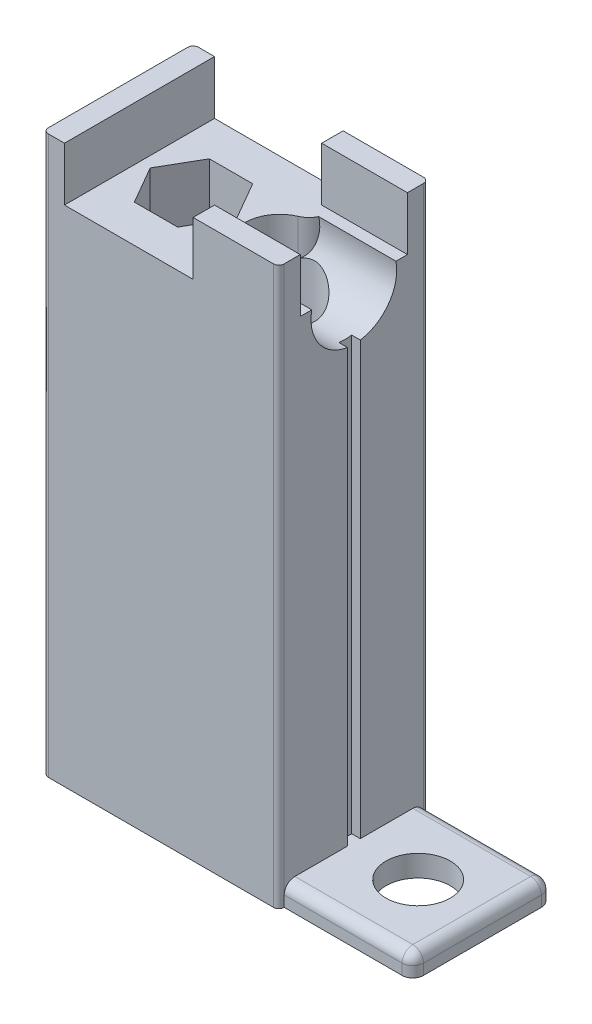
SolidWorks part; units mm, degrees
ref_plane "Front Plane" through (0, 0, 0) normal (0, 0, 1) x (1, 0, 0)
ref_plane "Top Plane" through (0, 0, 0) normal (0, 1, 0) x (1, 0, 0)
ref_plane "Right Plane" through (0, 0, 0) normal (1, 0, 0) x (0, 0, -1)
sketch "Sketch1" plane through (0, 0, 0) normal (0, 1, 0) x (1, 0, 0)
  line L1 (0, 0) -> (22, 0)
  line L2 (0, 0) -> (0, 14)
  line L3 (0, 14) -> (22, 14)
  line L4 (22, 0) -> (22, 14)
  dimension "D1" = 22
  dimension "D2" = 14
extrude "Boss-Extrude1" add sketch "Sketch1" along normal blind 47
sketch "Sketch2" plane through (0, 47, 0) normal (0, 1, 0) x (1, 0, 0)
  line L0 (22, 0) -> (22, 2)
  line L1 (22, 0) -> (22, 14) construction
  line L2 (0, 14) -> (2, 14)
  line L3 (22, 14) -> (0, 14) construction
  line L4 (2, 14) -> (2, 0)
  line L5 (22, 12) -> (22, 14)
  line L6 (0, 0) -> (22, 0) construction
  line L7 (0, 14) -> (0, 0)
  line L8 (2, 0) -> (0, 0)
  line L9 (22, 14) -> (14, 14)
  line L10 (14, 14) -> (14, 12)
  line L11 (14, 12) -> (22, 12)
  line L12 (22, 2) -> (14, 2)
  line L13 (14, 2) -> (14, 0)
  line L14 (14, 0) -> (22, 0)
  dimension "D1" = 2
  dimension "D2" = 2
  dimension "D3" = 8
  dimension "D4" = 8
  dimension "D5" = 2
extrude "Boss-Extrude2" add sketch "Sketch2" along normal blind 5
sketch "Sketch3" plane through (0, 47, 0) normal (0, 1, 0) x (1, 0, 0)
  line L0 (2, 0) -> (2, 14) construction
  line L2 (0, 7) -> (22, 7) construction
  line L4 (0, 14) -> (0, 0) construction
  line L5 (22, 2) -> (22, 12) construction
  line L7 (11.0829, 7) -> (9.0622, 10.5)
  line L8 (9.0622, 10.5) -> (5.0207, 10.5)
  line L9 (5.0207, 10.5) -> (3, 7)
  line L10 (3, 7) -> (5.0207, 3.5)
  line L13 (5.0207, 3.5) -> (9.0622, 3.5)
  line L14 (9.0622, 3.5) -> (11.0829, 7)
  circle A0 centre (7.0415, 7) radius 3.5 construction
  circle A1 centre (15.0829, 7) radius 3.25
  dimension "D1" = 7
  dimension "D2" = 1
  dimension "D3" = 6.5
  dimension "D4" = 4
extrude "Cut-Extrude1" cut sketch "Sketch3" against normal through all
sketch "Sketch4" plane through (22, 0, 0) normal (1, 0, 0) x (0, 0, -1)
  line L0 (7, 52) -> (7, 0) construction
  line L2 (0, 52) -> (14, 52) construction
  line L4 (0, 0) -> (14, 0) construction
  line L5 (0, 47) -> (14, 47) construction
  line L6 (6.4, 47) -> (7.6, 47)
  line L7 (6.4, 47) -> (6.4, 0)
  line L9 (6.4, 0) -> (7.6, 0)
  line L10 (7.6, 47) -> (7.6, 0)
  dimension "D1" = 1.2
  dimension "D2" = 0.6
extrude "Cut-Extrude2" cut sketch "Sketch4" against normal blind 0.8
sketch "Sketch5" plane through (22, 0, 0) normal (1, 0, 0) x (0, 0, -1)
  line L0 (7, 52) -> (7, 0) construction
  line L1 (0, 52) -> (14, 52) construction
  line L2 (6.4, 0) -> (7.6, 0) construction
  circle A0 centre (7, 46.25) radius 4
  dimension "D1" = 8
  dimension "D3" = 5.75
extrude "Cut-Extrude3" cut sketch "Sketch5" against normal blind 7
sketch "Sketch7" plane through (0, 0, 0) normal (-1, 0, 0) x (0, 0, 1)
  line L0 (-14, 52) -> (0, 52) construction
  line L2 (-14, 52) -> (-14, 0) construction
  text T0 "<b>Oufff</b>\r\n<b>TEAM</b>"
  dimension "D1" = 20
  dimension "D2" = 1
extrude "Cut-Extrude4" cut sketch "Sketch7" against normal blind 1
fillet "Fillet1" radius 2 2 edges at (15, 45.4583, -10.2489) (15, 45.4583, -3.7511)
fillet "Fillet2" radius 0.5 4 edges at (0, 26, -14) (22, 26, -14) (0, 26, 0) (22, 26, 0)
sketch "Sketch8" plane through (22, 0, 0) normal (1, 0, 0) x (0, 0, -1)
  line L1 (13.5, 0) -> (13.5, 52) construction
  line L2 (0.5, 0) -> (13.5, 0)
  line L3 (0.5, 0) -> (0.5, 2)
  line L4 (0.5, 2) -> (13.5, 2)
  line L7 (13.5, 0) -> (13.5, 2)
  dimension "D1" = 2
extrude "Boss-Extrude3" add sketch "Sketch8" along normal blind 12 and the other way blind 1
fillet "Fillet4" radius 1 5 edges at (34, 1, -13.5) (34, 1, -0.5) (28, 2, -13.5) (34, 2, -7) (28, 2, -0.5)
sketch "Sketch9" plane through (0, 2, 0) normal (0, 1, 0) x (1, 0, 0)
  line L0 (34, 7) -> (16.9331, 7) construction
  line L1 (34, 12.5) -> (34, 1.5) construction
  circle A0 centre (28, 7) radius 3
  dimension "D1" = 6
  dimension "D2" = 6
extrude "Cut-Extrude5" cut sketch "Sketch9" against normal through all
